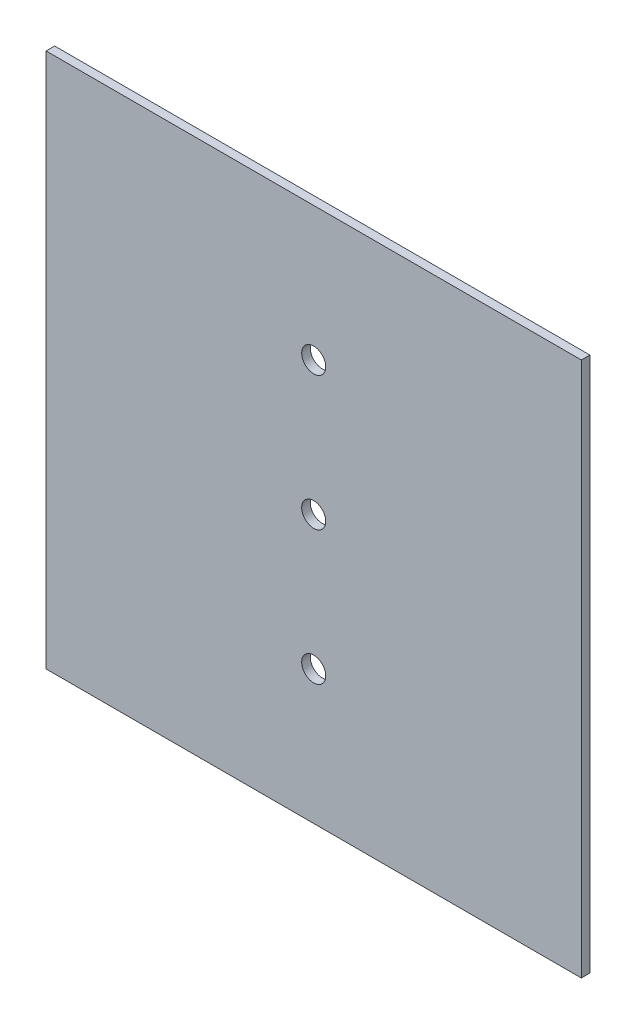
SolidWorks part; units mm, degrees
material "Copper"
ref_plane "Front Plane" through (0, 0, 0) normal (0, 0, 1) x (1, 0, 0)
ref_plane "Top Plane" through (0, 0, 0) normal (0, 1, 0) x (1, 0, 0)
ref_plane "Right Plane" through (0, 0, 0) normal (1, 0, 0) x (0, 0, -1)
sketch "Sketch1" plane through (0, 0, 0) normal (0, 0, 1) x (1, 0, 0)
  line L1 (-50, -50) -> (50, -50)
  line L2 (-50, -50) -> (-50, 50)
  line L3 (-50, 50) -> (50, 50)
  line L4 (50, -50) -> (50, 50)
  line L5 (-50, -50) -> (50, 50) construction
  line L6 (-50, 50) -> (50, -50) construction
  dimension "D1" = 100
extrude "Boss-Extrude1" add sketch "Sketch1" along normal blind 1.6
sketch "Sketch2" [suppressed] plane through (0, 0, 1.6) normal (0, 0, 1) x (1, 0, 0)
  circle A0 centre (0, 0) radius 50
  line M2 (50, -50) -> (50, 50)
  line M3 (50, 50) -> (-50, 50)
  line M4 (-50, 50) -> (-50, -50)
  line M5 (-50, -50) -> (50, -50)
  dimension "D1" = 100
extrude "Cut-Extrude1" [suppressed] cut sketch "Sketch2" against normal blind 1.6 contours A0 M3 M4 | A0 M4 M5 | A0 M5 M2 | A0 M2 M3
sketch "Sketch3" plane through (0, 0, 0) normal (0, 0, -1) x (-1, 0, 0)
  circle A2 centre (0, 0) radius 2.2479 construction
  circle A3 centre (0, 0) radius 2.2479
  circle A4 centre (0, -25) radius 2.2479 construction
  circle A5 centre (0, -25) radius 2.2479
  circle A6 centre (0, 25) radius 2.2479 construction
  circle A7 centre (0, 25) radius 2.2479
extrude "Cut-Extrude2" cut sketch "Sketch3" against normal up to surface (1.6 mm away) up to face at (0, 0, 1.6)
